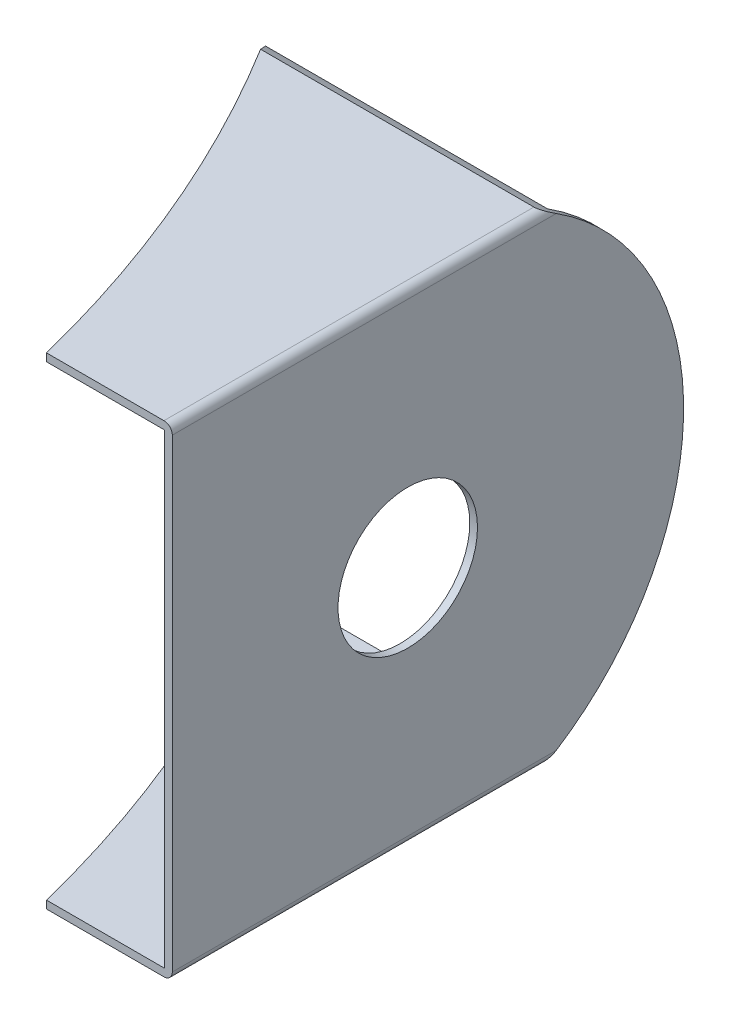
SolidWorks part; units mm, degrees
note: The reader was unsure of these and kept them because the rebuilt part matched: flange length of "Edge-Flange1".
material "Galvanized Steel"
ref_plane "Front Plane" through (0, 0, 0) normal (0, 0, 1) x (1, 0, 0)
ref_plane "Top Plane" through (0, 0, 0) normal (0, 1, 0) x (1, 0, 0)
ref_plane "Right Plane" through (0, 0, 0) normal (1, 0, 0) x (0, 0, -1)
sketch "Sketch1" plane through (0, 0, 0) normal (1, 0, 0) x (0, 0, -1)
  line L1 (-365, -75) -> (365, -75)
  line L2 (-365, -75) -> (-365, 75)
  line L3 (-365, 75) -> (365, 75)
  line L4 (365, -75) -> (365, 75)
  line L5 (-365, -75) -> (365, 75) construction
  line L6 (-365, 75) -> (365, -75) construction
  point P0 (0, 0)
  dimension "D1" = 150
  dimension "D2" = 730
base flange "Base-Flange1" sketch "Sketch1" thickness 2.5 reverse thickness direction no parameters "D1"=0.2
edge flange "Edge-Flange1" sketch "Sketch10" flange profiles "Sketch10", "Sketch11" flange angle 90 flange length 130 flange position bend outside bend radius 0.2 thickness 2.5 relief rectangular parameters "D6"=10, "D8"=1
sketch "Sketch10" plane through (-2.5, 75, 0) normal (0, -1, 0) x (0, 0, 1)
  line L2 (-365, 0) -> (-365, 127.5)
  line L3 (-365, 127.5) -> (365, 127.5)
  line L4 (365, 127.5) -> (365, 0)
  line L5 (365, 0) -> (-365, 0) construction
  line L6 (365, 0) -> (-365, 0)
sketch "Sketch11" plane through (-2.5, -75, 0) normal (0, 1, 0) x (0, 0, -1)
  line L0 (365, 0) -> (-365, 0) construction
  line L1 (365, 0) -> (-365, 0)
  line L2 (365, 0) -> (365, 127.5)
  line L3 (365, 127.5) -> (-365, 127.5)
  line L4 (-365, 127.5) -> (-365, 0)
bend "EdgeBend1" bend radius 0.2 bend angle 90 parameters "D5"=1
bend "EdgeBend2" bend radius 0.2 bend angle 90 parameters "D5"=2
sketch "Sketch12" plane through (0, 77.7, 0) normal (0, 1, 0) x (1, 0, 0)
  line L1 (-130, 365) -> (-2.7, 365) construction
  line L2 (-130, -365) -> (-130, 365) construction
  circle A0 centre (-470, 85) radius 434
  dimension "D1" = 868
  dimension "D3" = 340
  dimension "D2" = 280
extrude "Cut-Extrude1" cut sketch "Sketch12" against normal through all both and the other way through all
sketch "Sketch13" plane through (0, 0, 0) normal (1, 0, 0) x (0, 0, -1)
  line L0 (365, -75) -> (365, 75) construction
  line L1 (-365, 75) -> (-365, -75) construction
  circle A0 centre (265, 0) radius 22.5
  circle A1 centre (-290, 0) radius 22.5
  dimension "D1" = 45
  dimension "D2" = 100
  dimension "D3" = 45
  dimension "D4" = 75
extrude "Cut-Extrude2" cut sketch "Sketch13" against normal blind 10
sketch "Sketch14" plane through (0, 0, 0) normal (1, 0, 0) x (0, 0, -1)
  line L1 (189.0395, 122.5591) -> (-442.2981, 122.5591)
  line L2 (189.0395, 122.5591) -> (189.0395, -150.5984)
  line L3 (189.0395, -150.5984) -> (-442.2981, -150.5984)
  line L4 (-442.2981, 122.5591) -> (-442.2981, -150.5984)
extrude "Cut-Extrude3" cut sketch "Sketch14" against normal through all both and the other way through all
sketch "Sketch15" plane through (0, 0, 0) normal (1, 0, 0) x (0, 0, -1)
  line L0 (302.2666, 80.8221) -> (310.532, 105.3518)
  line L1 (310.532, 105.3518) -> (400.6684, 94.5662)
  line L2 (400.6684, 94.5662) -> (380.2529, -108.0482)
  line L3 (380.2529, -108.0482) -> (291.2869, -85.0294)
  arc A0 (291.2869, -85.0294) -> (302.2666, 80.8221) centre (265, 0) ccw
  dimension "D1" = 178
extrude "Cut-Extrude4" cut sketch "Sketch15" against normal through all both and the other way through all
sketch "Sketch16" plane through (0, -77.7, 0) normal (0, -1, 0) x (1, 0, 0)
  line L0 (-39.2895, -183.7533) -> (-75.5282, -178.563)
  line L1 (-75.5282, -178.563) -> (-125.0049, -316.5305)
  line L2 (-125.0049, -316.5305) -> (-101.5855, -324.9289)
  circle A0 centre (-454.1992, -85) radius 426.5 construction
  arc A1 (-101.5855, -324.9289) -> (-39.2895, -183.7533) centre (-454.1992, -85) ccw
extrude "Cut-Extrude5" cut sketch "Sketch16" against normal through all normal cut yes
sketch "Bend-Lines1" [suppressed] plane through (0, 0, 0) normal (0, 1, 0) x (1, 0, 0)
sketch "Bounding-Box1" [suppressed] plane through (0, 0, 0) normal (0, 1, 0) x (1, 0, 0)
sheet metal parameters "Sheet-Metal1" thickness 2.5 parameters "D1"=0.2
flat pattern "Flat-Pattern1" [suppressed]
sketch "Bend-Lines2" plane through (0, 0, 0) normal (0, 1, 0) x (1, 0, 0)
sketch3d "Bounding-Box2" [suppressed]
  line L0 (-227, -60, 0) -> (227, -60, 0) construction
  line L1 (-227, 60, 0) -> (227, 60, 0) construction
  line L2 (-227, -60, 0) -> (-227, 60, 0) construction
  line L3 (227, -60, 0) -> (227, 60, 0) construction
sheet metal parameters "Sheet-Metal2" thickness 2.5 parameters "D1"=0.2
flat pattern "Flat-Pattern1"
sketch "Bend-Lines2" plane through (0, 0, 0) normal (1, 0, 0) x (0, 0, -1)
  line L0 (-227, -61.1388) -> (227, -61.1388) construction
  line L1 (227, 61.1388) -> (-227, 61.1388) construction
  line L2 (-227, -61.1388) -> (227, -61.1388) construction
  line L3 (227, 61.1388) -> (-227, 61.1388) construction
sketch3d "Bounding-Box2" [suppressed]
  line L0 (227, -139.5777, 0) -> (-227, -139.5777, 0) construction
  line L1 (227, 139.5777, 0) -> (-227, 139.5777, 0) construction
  line L2 (227, -139.5777, 0) -> (227, 139.5777, 0) construction
  line L3 (-227, -139.5777, 0) -> (-227, 139.5777, 0) construction
bend of the flat pattern "Flatten-<EdgeBend1>1"
bend of the flat pattern "Flatten-<EdgeBend2>1"
sheet metal parameters "Sheet-Metal3" thickness 2.5 parameters "D1"=0.2
flat pattern "Flat-Pattern1"
sketch "Bend-Lines2" plane through (0, 0, 0) normal (1, 0, 0) x (0, 0, -1)
  line L0 (-227, -61.1388) -> (227, -61.1388) construction
  line L1 (227, 61.1388) -> (-227, 61.1388) construction
  line L2 (-227, -61.1388) -> (227, -61.1388) construction
  line L3 (227, 61.1388) -> (-227, 61.1388) construction
sketch3d "Bounding-Box2" [suppressed]
  line L0 (227, -132.9694, 0) -> (-227, -132.9694, 0) construction
  line L1 (227, 132.9694, 0) -> (-227, 132.9694, 0) construction
  line L2 (227, -132.9694, 0) -> (227, 132.9694, 0) construction
  line L3 (-227, -132.9694, 0) -> (-227, 132.9694, 0) construction
bend of the flat pattern "Flatten-<EdgeBend1>1"
bend of the flat pattern "Flatten-<EdgeBend2>1"
sheet metal parameters "Sheet-Metal4" thickness 2.5 parameters "D1"=0.2
flat pattern "Flat-Pattern1"
sketch "Bend-Lines2" plane through (0, 0, 0) normal (1, 0, 0) x (0, 0, -1)
  line L0 (-340, -61.1388) -> (340, -61.1388) construction
  line L1 (340, 61.1388) -> (-340, 61.1388) construction
  line L2 (-340, -61.1388) -> (340, -61.1388) construction
  line L3 (340, 61.1388) -> (-340, 61.1388) construction
sketch3d "Bounding-Box2" [suppressed]
  line L0 (340, -177.6863, 0) -> (-340, -177.6863, 0) construction
  line L1 (340, 177.6863, 0) -> (-340, 177.6863, 0) construction
  line L2 (340, -177.6863, 0) -> (340, 177.6863, 0) construction
  line L3 (-340, -177.6863, 0) -> (-340, 177.6863, 0) construction
bend of the flat pattern "Flatten-<EdgeBend1>1"
bend of the flat pattern "Flatten-<EdgeBend2>1"
sheet metal parameters "Sheet-Metal7" thickness 2.5 parameters "D1"=0.2
flat pattern "Flat-Pattern1"
sketch "Bend-Lines2" plane through (0, 0, 0) normal (1, 0, 0) x (0, 0, -1)
  line L0 (189.0395, -76.1388) -> (365, -76.1388) construction
  line L1 (365, 76.1388) -> (189.0395, 76.1388) construction
  line L2 (189.0395, -76.1388) -> (365, -76.1388) construction
  line L3 (365, 76.1388) -> (189.0395, 76.1388) construction
sketch3d "Bounding-Box2" [suppressed]
  line L0 (189.0395, 204.5777, 0) -> (189.0395, -204.5777, 0) construction
  line L1 (365, 204.5777, 0) -> (365, -204.5777, 0) construction
  line L2 (189.0395, 204.5777, 0) -> (365, 204.5777, 0) construction
  line L3 (189.0395, -204.5777, 0) -> (365, -204.5777, 0) construction
bend of the flat pattern "Flatten-<EdgeBend1>1"
bend of the flat pattern "Flatten-<EdgeBend2>1"
sheet metal parameters "Sheet-Metal8" thickness 2.5 parameters "D1"=0.2
flat pattern "Flat-Pattern1"
sketch "Bend-Lines2" plane through (0, 0, 0) normal (1, 0, 0) x (0, 0, -1)
  line L0 (312.7593, -76.1388) -> (189.0395, -76.1388) construction
  line L1 (308.559, 76.1388) -> (189.0395, 76.1388) construction
  line L2 (312.7593, -76.1388) -> (189.0395, -76.1388) construction
  line L3 (308.559, 76.1388) -> (189.0395, 76.1388) construction
sketch3d "Bounding-Box2" [suppressed]
  line L0 (189.0395, 172.4921, 0) -> (189.0395, -172.4921, 0) construction
  line L1 (354, 172.4921, 0) -> (354, -172.4921, 0) construction
  line L2 (189.0395, 172.4921, 0) -> (354, 172.4921, 0) construction
  line L3 (189.0395, -172.4921, 0) -> (354, -172.4921, 0) construction
bend of the flat pattern "Flatten-<EdgeBend1>1"
bend of the flat pattern "Flatten-<EdgeBend2>1"
sheet metal parameters "Sheet-Metal9" thickness 2.5 parameters "D1"=0.2
flat pattern "Flat-Pattern9" [suppressed]
sketch "Bend-Lines3" plane through (0, 0, 0) normal (0, 1, 0) x (1, 0, 0)
sketch "Bounding-Box3" [suppressed] plane through (0, 0, 0) normal (0, 1, 0) x (1, 0, 0)
bend of the flat pattern "Flatten-<EdgeBend2>2"
bend of the flat pattern "Flatten-<EdgeBend1>2"
sheet metal parameters "Sheet-Metal10" thickness 2.5 parameters "D1"=0.2
flat pattern "Flat-Pattern10"
sketch "Bend-Lines4" plane through (0, 0, 0) normal (1, 0, 0) x (0, 0, -1)
  line L0 (-117.1198, -76.1388) -> (-365, -76.1388) construction
  line L1 (-123.9871, 76.1388) -> (-365, 76.1388) construction
  line L2 (-117.1198, -76.1388) -> (-365, -76.1388) construction
  line L3 (-123.9871, 76.1388) -> (-365, 76.1388) construction
sketch3d "Bounding-Box4" [suppressed]
  line L0 (-365, 204.5777, 0) -> (-365, -204.5777, 0) construction
  line L1 (-116.8515, 204.5777, 0) -> (-116.8515, -204.5777, 0) construction
  line L2 (-365, 204.5777, 0) -> (-116.8515, 204.5777, 0) construction
  line L3 (-365, -204.5777, 0) -> (-116.8515, -204.5777, 0) construction
bend of the flat pattern "Flatten-<EdgeBend2>3"
bend of the flat pattern "Flatten-<EdgeBend1>3"
sheet metal parameters "Sheet-Metal11" thickness 2.5 parameters "D1"=0.2
flat pattern "Flat-Pattern1"
sketch "Bend-Lines2" plane through (0, 0, 0) normal (1, 0, 0) x (0, 0, -1)
  line L0 (312.7593, -76.1388) -> (189.0395, -76.1388) construction
  line L1 (308.559, 76.1388) -> (189.0395, 76.1388) construction
  line L2 (312.7593, -76.1388) -> (189.0395, -76.1388) construction
  line L3 (308.559, 76.1388) -> (189.0395, 76.1388) construction
sketch3d "Bounding-Box2" [suppressed]
  line L0 (189.0395, 165.4671, 0) -> (189.0395, -165.4671, 0) construction
  line L1 (354, 165.4671, 0) -> (354, -165.4671, 0) construction
  line L2 (189.0395, 165.4671, 0) -> (354, 165.4671, 0) construction
  line L3 (189.0395, -165.4671, 0) -> (354, -165.4671, 0) construction
bend of the flat pattern "Flatten-<EdgeBend1>1"
bend of the flat pattern "Flatten-<EdgeBend2>1"
